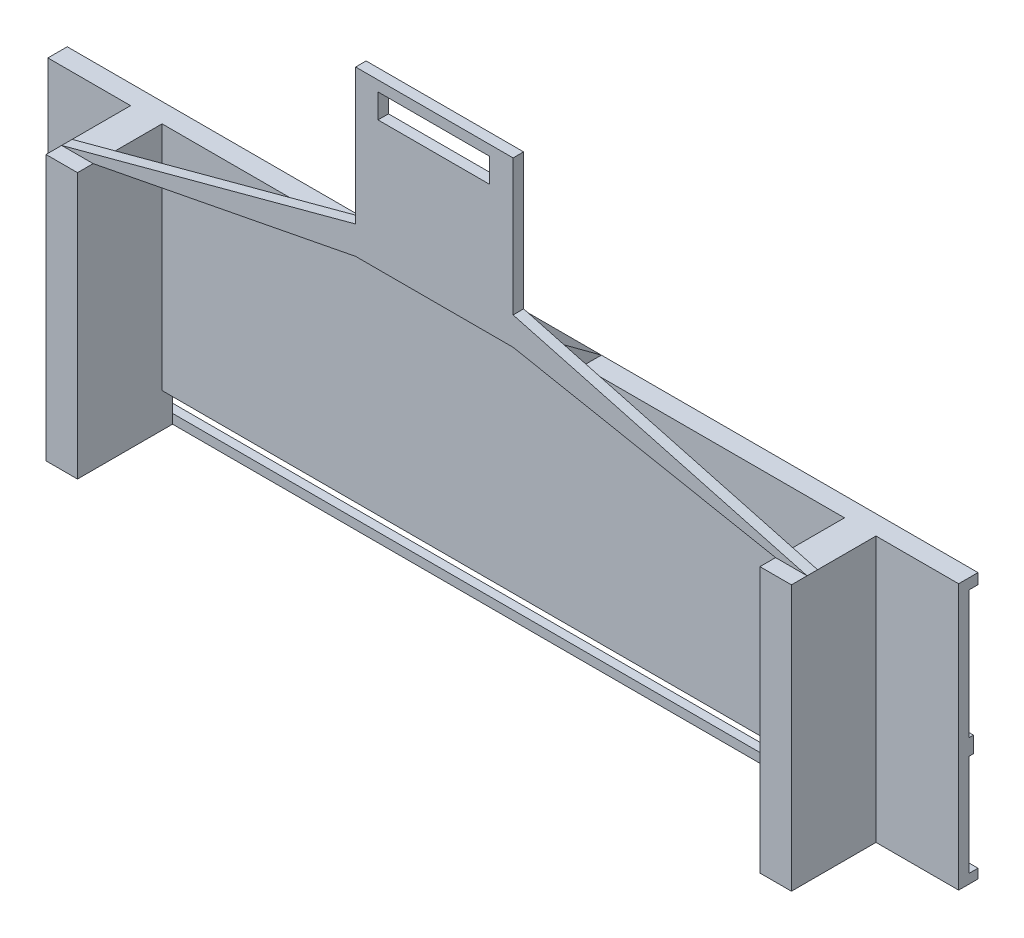
SolidWorks part; units mm, degrees
ref_plane "Front Plane" through (0, 0, 0) normal (0, 0, 1) x (1, 0, 0)
ref_plane "Top Plane" through (0, 0, 0) normal (0, 1, 0) x (1, 0, 0)
ref_plane "Right Plane" through (0, 0, 0) normal (1, 0, 0) x (0, 0, -1)
sketch "Sketch1" plane through (0, 0, 0) normal (0, 0, 1) x (1, 0, 0)
  line L1 (0, 0) -> (165.1, 0)
  line L2 (0, 0) -> (0, 55.88)
  line L3 (0, 55.88) -> (165.1, 55.88)
  line L4 (165.1, 0) -> (165.1, 55.88)
  line L5 (0, 0) -> (-7.62, 0)
  line L6 (0, 0) -> (0, 55.88)
  line L7 (0, 55.88) -> (-7.62, 55.88)
  line L8 (-7.62, 0) -> (-7.62, 55.88)
  line L9 (165.1, 0) -> (172.72, 0)
  line L10 (165.1, 0) -> (165.1, 55.88)
  line L11 (165.1, 55.88) -> (172.72, 55.88)
  line L12 (172.72, 0) -> (172.72, 55.88)
  dimension "D1" = 7.62
  dimension "D2" = 7.62
  dimension "D3" = 165.1
  dimension "D4" = 55.88
extrude "Boss-Extrude1" add sketch "Sketch1" along normal blind 2.54 contours L1 L4 L3 L2 region at (82.55, 27.94, 0)
extrude "Boss-Extrude2" add sketch "Sketch1<3>" along normal blind 20 contours L8 L5 L2 L7 | L9 L12 L11 L4 region at (-3.81, 27.94, 0) region at (168.91, 27.94, 0)
sketch "Sketch1<3>" plane through (0, 0, 0) normal (0, 0, 1) x (1, 0, 0) same geometry as "Sketch1"
sketch "Sketch2" plane through (0, 55.88, 0) normal (0, 1, 0) x (1, 0, 0)
  line L0 (165.1, 0) -> (192.72, 0)
  line L1 (-7.62, 0) -> (172.72, 0) construction
  line L2 (192.72, 0) -> (192.72, -2.54)
  line L3 (192.72, -2.54) -> (172.72, -2.54)
  line L4 (172.72, -20) -> (172.72, 0) construction
  line L5 (172.72, -2.54) -> (172.72, -23)
  line L6 (172.72, -23) -> (165.1, -23)
  line L7 (165.1, -23) -> (165.1, 0)
  dimension "D1" = 2.54
  dimension "D2" = 20
  dimension "D3" = 23
extrude "Boss-Extrude3" add sketch "Sketch2" against normal blind 64.2
ref_plane "Plane1" through (82.55, 0, 0) normal (1, 0, 0) x (0, 0, -1)
sketch "Sketch3" plane through (82.55, 0, 0) normal (1, 0, 0) x (0, 0, -1)
  line L0 (0, -8.32) -> (0, 55.88) construction
  line L1 (0, 55.88) -> (2.1398, 55.88)
  line L2 (0, 55.88) -> (0, 53.3329)
  line L3 (0, 53.3329) -> (2.1398, 53.3329)
  line L4 (2.1398, 55.88) -> (2.1398, 53.3329)
  line L5 (0, -8.32) -> (2.1398, -8.32)
  line L6 (0, -8.32) -> (0, -6.0571)
  line L7 (0, -6.0571) -> (2.1398, -6.0571)
  line L8 (2.1398, -8.32) -> (2.1398, -6.0571)
  line L9 (0, 22.3592) -> (1.0699, 22.3592)
  line L10 (0, 22.3592) -> (0, 18.4756)
  line L11 (0, 18.4756) -> (1.0699, 18.4756)
  line L12 (1.0699, 22.3592) -> (1.0699, 18.4756)
extrude "Boss-Extrude4" add sketch "Sketch3" along normal up to surface (110.17 mm away) up to face at (192.72, 23.78, 1.27)
mirror "Mirror1" about plane through (82.55, 0, 0) normal (1, 0, 0) of "Boss-Extrude3", "Boss-Extrude4"
sketch "Sketch4" plane through (82.55, 0, 0) normal (1, 0, 0) x (0, 0, -1)
  line L0 (2.1398, 55.88) -> (-16.6708, 69.7731)
  line L1 (-16.6708, 69.7731) -> (-16.6708, 107.8731)
  line L2 (-16.6708, 107.8731) -> (-19.2108, 107.8731)
  line L3 (-19.2108, 107.8731) -> (-19.2108, 68.1927)
  line L4 (-19.2108, 68.1927) -> (-2.54, 55.88)
  line L5 (-2.54, 55.88) -> (2.1398, 55.88)
  dimension "D1" = 2.54
  dimension "D2" = 38.1
extrude "Boss-Extrude5" add sketch "Sketch4" along normal mid plane 38.1 contours L4 L5 L0 L1 L2 L3 region at (82.55, 56.4421, 0.2001)
sketch "Sketch5" plane through (0, 0, 19.2108) normal (0, 0, 1) x (1, 0, 0)
  line L0 (63.5, 68.1927) -> (0, 55.88)
  line L1 (0, 55.88) -> (-7.62, 55.88)
  line L2 (-7.62, 55.88) -> (63.5, 74.9732)
  line L3 (63.5, 107.8731) -> (63.5, 68.1927) construction
  line L4 (63.5, 74.9732) -> (63.5, 68.1927)
  line L5 (82.55, -12.65) -> (82.55, 12.65) construction
  line L6 (101.6, 74.9732) -> (101.6, 68.1927)
  line L7 (172.72, 55.88) -> (101.6, 74.9732)
  line L8 (165.1, 55.88) -> (172.72, 55.88)
  line L9 (101.6, 68.1927) -> (165.1, 55.88)
extrude "Boss-Extrude6" add sketch "Sketch5" against normal up to surface (2.54 mm away) up to face at (82.55, 88.8231, 16.6708)
sketch "Sketch6" plane through (0, 0, 19.2108) normal (0, 0, 1) x (1, 0, 0)
  line L1 (68.9113, 105.3641) -> (95.8715, 105.3641)
  line L2 (68.9113, 105.3641) -> (68.9113, 99.4963)
  line L3 (68.9113, 99.4963) -> (95.8715, 99.4963)
  line L4 (95.8715, 105.3641) -> (95.8715, 99.4963)
extrude "Cut-Extrude1" cut sketch "Sketch6" against normal through all
